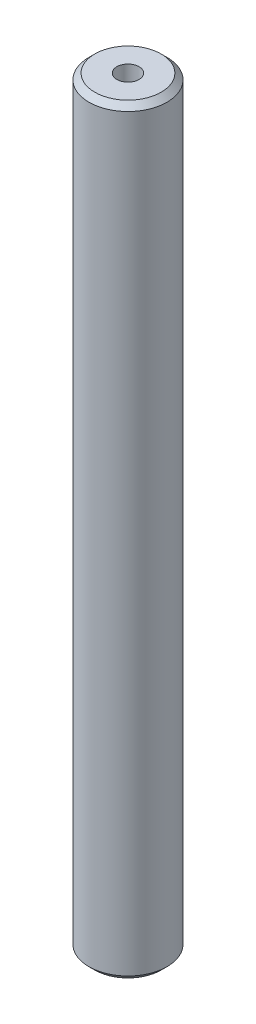
SolidWorks part; units mm, degrees
ref_plane "Front Plane" through (0, 0, 0) normal (0, 0, 1) x (1, 0, 0)
ref_plane "Top Plane" through (0, 0, 0) normal (0, 1, 0) x (1, 0, 0)
ref_plane "Right Plane" through (0, 0, 0) normal (1, 0, 0) x (0, 0, -1)
sketch "Sketch1" plane through (0, 0, 0) normal (0, 1, 0) x (1, 0, 0)
  circle A0 centre (0, 0) radius 5
  dimension "SHAFT_OD" = 10
extrude "Boss-Extrude1" add sketch "Sketch1" along normal blind 97.566
sketch "Sketch2" plane through (0, 0, 0) normal (0, 1, 0) x (1, 0, 0)
  circle A0 centre (0, 0) radius 1.4277
  dimension "BORE_D" = 2.8554
extrude "Cut-Extrude1" cut sketch "Sketch2" along normal through all
chamfer "Chamfer1" distance 0.7414 angle 45 2 edges at (0, 97.566, 5) (0, 0, 5)
